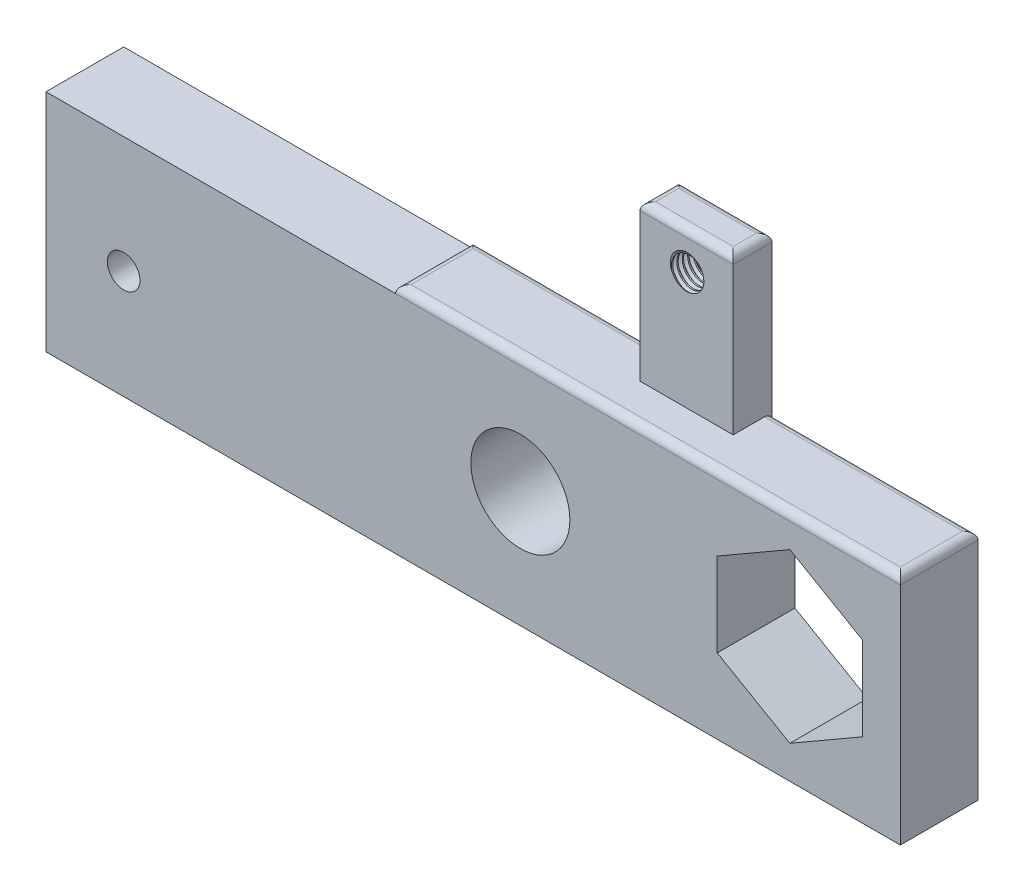
SolidWorks part; units mm, degrees
ref_plane "Front Plane" through (0, 0, 0) normal (0, 0, 1) x (1, 0, 0)
ref_plane "Top Plane" through (0, 0, 0) normal (0, 1, 0) x (1, 0, 0)
ref_plane "Right Plane" through (0, 0, 0) normal (1, 0, 0) x (0, 0, -1)
sketch "Sketch1" plane through (0, 0, 0) normal (0, 0, 1) x (1, 0, 0)
  line L1 (-32.5, 15) -> (32.5, 15)
  line L2 (-32.5, 15) -> (-32.5, -15)
  line L3 (-32.5, -15) -> (32.5, -15)
  line L4 (32.5, 15) -> (32.5, -15)
  line L5 (0, -15) -> (0, 15) construction
  line L6 (-32.5, 0) -> (32.5, 0) construction
  point P0 (0, 0)
  dimension "D1" = 30
  dimension "D2" = 65
extrude "Boss-Extrude1" add sketch "Sketch1" along normal blind 10
sketch "Sketch2" plane through (0, 0, 10) normal (0, 0, 1) x (1, 0, 0)
  line L4 (18.2794, -10.7603) -> (27.6325, -5.3603)
  line L5 (27.6325, -5.3603) -> (27.6325, 5.4397)
  line L6 (27.6325, 5.4397) -> (18.2794, 10.8397)
  line L7 (18.2794, 10.8397) -> (8.9263, 5.4397)
  line L8 (8.9263, 5.4397) -> (8.9263, -5.3603)
  line L9 (8.9263, -5.3603) -> (18.2794, -10.7603)
  circle A0 centre (-16.4237, -0.0241) radius 6.375
  dimension "D1" = 12.75
  dimension "D2" = 10.8
  dimension "D3" = 34.7031
extrude "Cut-Extrude1" cut sketch "Sketch2" against normal blind 10
sketch "Sketch4" plane through (0, 15, 0) normal (0, 1, 0) x (1, 0, 0)
  line L8 (-6, -0.0243) -> (6, -0.0243)
  line L13 (-6, -0.0243) -> (-6, -5.0243)
  line L14 (-6, -5.0243) -> (6, -5.0243)
  line L15 (6, -0.0243) -> (6, -5.0243)
  line L16 (0, -5.0243) -> (0, -0.0243) construction
  line L17 (-6, -2.5243) -> (6, -2.5243) construction
  point P0 (0, -2.5243)
  point P6 (0, -2.5243)
  dimension "D1" = 5
  dimension "D2" = 12
extrude "Boss-Extrude5" add sketch "Sketch4" along normal mid plane 40
sketch "Sketch9" plane through (0, 0, 0) normal (0, 0, -1) x (-1, 0, 0)
  circle A0 centre (0, 30) radius 2
extrude "Cut-Extrude3" cut sketch "Sketch9" against normal mid plane 60
thread "Thread1" pitch 0.7 method cut profile "Thread Profile2" start angle 0, offset 1, length 10, pitch 0.7, diameter 4
ref_plane "Plane2" through (2, 30, -0.9757) normal (0, -1, 0) x (1, 0, 0)
sketch "Thread Profile2" plane through (2, 30, -0.9757) normal (0, -1, 0) x (1, 0, 0)
  line L0 (0, 0) -> (0, 0.7) construction
  line L1 (0, 0) -> (0.3789, 0.2187)
  line L2 (0.3789, 0.2187) -> (0.3789, 0.3062)
  line L3 (0.3789, 0.3062) -> (0, 0.525)
  line L4 (0.3789, 0.2625) -> (0, 0.2625) construction
  line L11 (0, 0) -> (0, 0.525)
  point P2 (0, 0)
  dimension "Pitch" = 0.7
  dimension "Profile_Angle" = 60
  dimension "Profile_Land" = 0.0875
  dimension "Profile_Height" = 0.3789
fillet "Fillet1" radius 1 8 edges at (0, 15, 10) (0, 15, 0) (-32.5, 15, 5) (32.5, 15, 5) (0, 35, 5.0243) (0, 35, 0.0243) (6, 35, 2.5243) (-6, 35, 2.5243)
sketch "Sketch10" plane through (-32.5, 0, 0) normal (-1, 0, 0) x (0, 0, 1)
  line L1 (0, 14) -> (10, 14)
  line L2 (0, 14) -> (0, -15)
  line L3 (0, -15) -> (10, -15)
  line L4 (10, 14) -> (10, -15)
extrude "Boss-Extrude6" add sketch "Sketch10" along normal blind 45
sketch "Sketch11" plane through (0, 0, 10) normal (0, 0, 1) x (1, 0, 0)
  line L0 (-77.5, -15) -> (-77.5, 14) construction
  circle A0 centre (-67.5, -1) radius 2.1
  point P3 (-77.5, -0.5)
  dimension "D1" = 10
extrude "Cut-Extrude4" cut sketch "Sketch11" against normal blind 50
